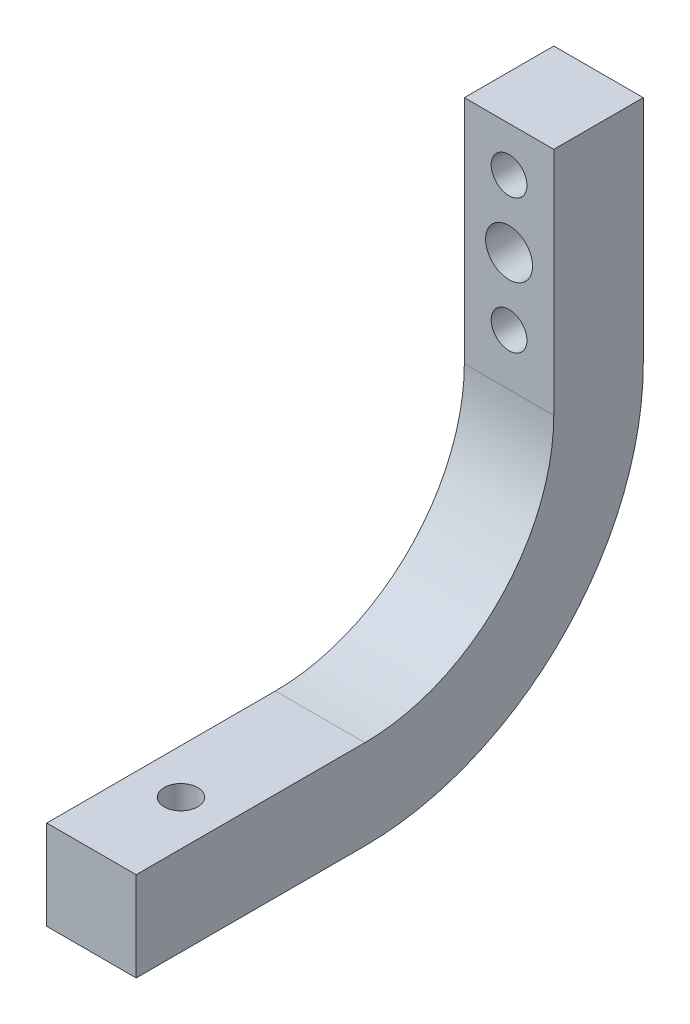
SolidWorks part; units mm, degrees
ref_plane "Front Plane" through (0, 0, 0) normal (0, 0, 1) x (1, 0, 0)
ref_plane "Top Plane" through (0, 0, 0) normal (0, 1, 0) x (1, 0, 0)
ref_plane "Right Plane" through (0, 0, 0) normal (1, 0, 0) x (0, 0, -1)
ref_axis "Z" through (0, 0, 47.607) along (0, 0, -1)
sketch "Sketch1" plane through (0, 0, 0) normal (1, 0, 0) x (0, 0, -1)
  line L0 (-8, 10) -> (0, 10)
  line L1 (0, 10) -> (0, -10.6067)
  line L2 (0, -18) -> (-17.5, -35.5) construction
  line L3 (-24.8933, -35.5) -> (-37.34, -35.5)
  line L4 (-37.34, -35.5) -> (-37.34, -27.5) construction
  line L5 (-37.34, -27.5) -> (-24.8933, -27.5)
  line L6 (-20.8137, -27.5) -> (-8, -14.6863) construction
  line L7 (-8, -10.6067) -> (-8, 10)
  line L8 (-14.4069, -21.0931) -> (-8.75, -26.75) construction
  line L9 (-24.8933, -27.5) -> (-20.8137, -27.5) construction
  line L10 (-37.34, -27.5) -> (-45.34, -27.5)
  line L11 (-37.34, -27.5) -> (-37.34, -35.5) construction
  line L12 (-37.34, -35.5) -> (-45.34, -35.5)
  line L13 (-45.34, -27.5) -> (-45.34, -35.5)
  line L14 (-8, -14.6863) -> (-8, -10.6067) construction
  line L15 (0, -10.6067) -> (0, -18) construction
  line L16 (-17.5, -35.5) -> (-24.8933, -35.5) construction
  arc A0 (-24.8933, -27.5) -> (-8, -10.6067) centre (-24.8933, -10.6067) ccw
  arc A1 (-24.8933, -35.5) -> (0, -10.6067) centre (-24.8933, -10.6067) ccw
  point P16 (0, 0)
  point P17 (2.9456, -7.9935)
  point P18 (-24.6991, -35.5)
  point P19 (-27.4554, -27.5)
  dimension "D1" = 8
  dimension "D2" = 37.34
  dimension "D3" = 35.5
  dimension "D4" = 10
  dimension "D5" = 135
  dimension "D6" = 17.5
  dimension "D7" = 8
  dimension "D8" = 12.4467
extrude "Boss-Extrude1" add sketch "Sketch1" along normal blind 4 and the other way blind 4
sketch "Sketch3" plane through (0, -27.5, 0) normal (0, 1, 0) x (1, 0, 0)
  line L0 (-55, 0) -> (55, 0) construction
  line L1 (0, -55) -> (0, 55) construction
  circle A0 centre (0, -37.34) radius 1.5
  dimension "D2" = 3
  dimension "D1" = 37.34
extrude "Cut-Extrude1" cut sketch "Sketch3" against normal through all
sketch "Sketch4" plane through (0, 0, 8) normal (0, 0, 1) x (1, 0, 0)
  line L0 (0, -6) -> (0, 6) construction
  circle A0 centre (0, 0) radius 2.1
  circle A1 centre (0, 6) radius 1.6
  circle A2 centre (0, -6) radius 1.6
  dimension "D1" = 4.2
  dimension "D3" = 3.2
  dimension "D2" = 12
extrude "Cut-Extrude2" cut sketch "Sketch4" against normal through all both and the other way through all
ref_axis "Axis1" through (0, -27.5, 37.34) along (0, 1, 0)
equation "\"rbracket-width\"=8"
equation "\"D1@Boss-Extrude1\"=\"rbracket-width\"/2"
equation "\"D2@Boss-Extrude1\"=\"rbracket-width\"/2"
equation "\"EyeCaptureRadius\"= ( \"EyeDiameter\" + \"EyeClearance\" ) / 2"
equation "\"rbracket_planetocenterline_dist\"= \"BasePlaneDistance\""
equation "\"D2@Sketch1\"=\"rbracket_planetocenterline_dist\""
equation "\"EyeDiameter\" = 35"
equation "\"BasePlaneDistance\" = \"EyeDiameter\"/2+19.84"
equation "\"EyeClearance\" = 2"
equation "\"D1@Sketch1\"=\"rbracket-width\""
equation "\"D3@Sketch1\"=(\"EyeDiameter\"+\"EyeClearance\"+\"EyeClearance\")/2 + \"L2Thickness\" + \"rbracket-width\""
equation "\"D4@Sketch1\"= 10"
equation "\"D6@Sketch1\"=\"EyeDiameter\"/2"
equation "\"D7@Sketch1\"=\"rbracket-width\""
equation "\"D1@Sketch3\"=\"BasePlaneDistance\""
equation "\"L2Thickness\" = 8"
equation "\"D8@Sketch1\"=\"rbracket_planetocenterline_dist\"/3"
